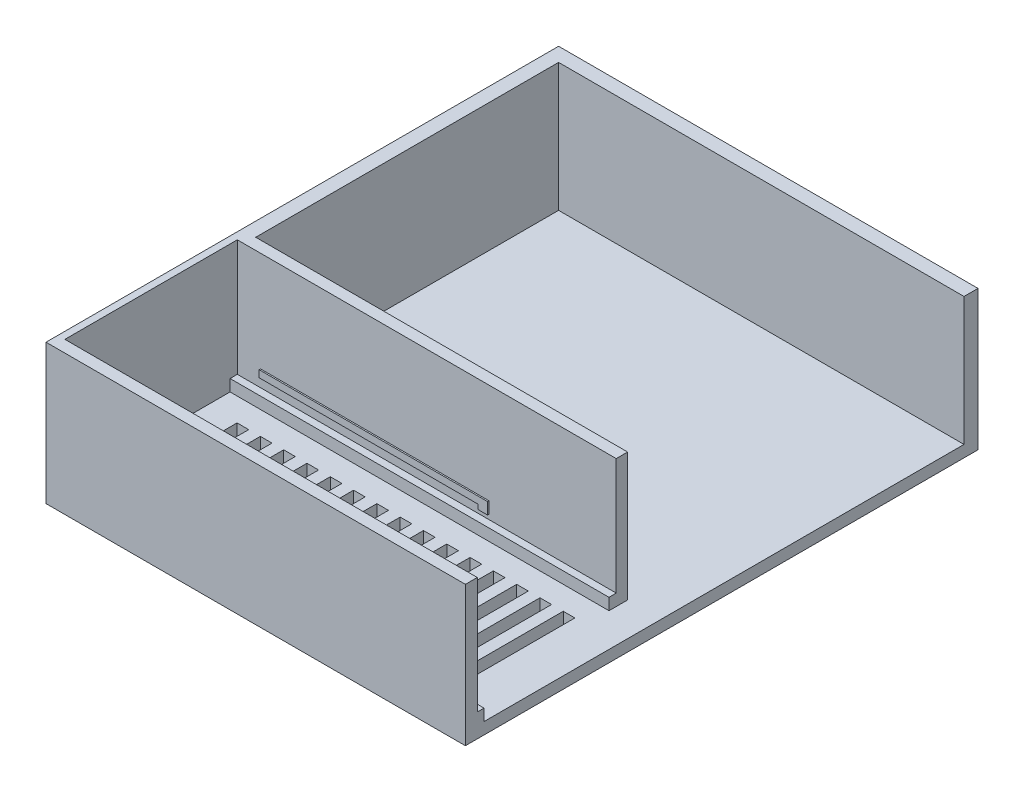
SolidWorks part; units mm, degrees
ref_plane "Front Plane" through (0, 0, 0) normal (0, 0, 1) x (1, 0, 0)
ref_plane "Top Plane" through (0, 0, 0) normal (0, 1, 0) x (1, 0, 0)
ref_plane "Right Plane" through (0, 0, 0) normal (1, 0, 0) x (0, 0, -1)
sketch "Sketch1" plane through (0, 0, 0) normal (0, 1, 0) x (1, 0, 0)
  line L0 (-32, -22) -> (-32, -47)
  line L1 (45, 55) -> (-45, 55)
  line L2 (45, 55) -> (45, -55)
  line L3 (45, -55) -> (-45, -55)
  line L4 (-45, 55) -> (-45, -55)
  line L5 (45, 55) -> (-45, -55) construction
  line L6 (45, -55) -> (-45, 55) construction
  line L7 (-37, -22) -> (-34.5, -22)
  line L8 (-37, -22) -> (-37, -47)
  line L9 (-37, -47) -> (-34.5, -47)
  line L10 (-34.5, -22) -> (-34.5, -47)
  line L11 (-32, -22) -> (-29.5, -22)
  line L12 (-29.5, -22) -> (-29.5, -47)
  line L13 (-32, -47) -> (-29.5, -47)
  line L14 (-27, -22) -> (-27, -47)
  line L15 (-27, -22) -> (-24.5, -22)
  line L16 (-24.5, -22) -> (-24.5, -47)
  line L17 (-27, -47) -> (-24.5, -47)
  line L18 (-22, -22) -> (-22, -47)
  line L19 (-22, -22) -> (-19.5, -22)
  line L20 (-19.5, -22) -> (-19.5, -47)
  line L21 (-22, -47) -> (-19.5, -47)
  line L22 (-17, -22) -> (-17, -47)
  line L23 (-17, -22) -> (-14.5, -22)
  line L24 (-14.5, -22) -> (-14.5, -47)
  line L25 (-17, -47) -> (-14.5, -47)
  line L26 (-12, -22) -> (-12, -47)
  line L27 (-12, -22) -> (-9.5, -22)
  line L28 (-9.5, -22) -> (-9.5, -47)
  line L29 (-12, -47) -> (-9.5, -47)
  line L30 (-7, -22) -> (-7, -47)
  line L31 (-7, -22) -> (-4.5, -22)
  line L32 (-4.5, -22) -> (-4.5, -47)
  line L33 (-7, -47) -> (-4.5, -47)
  line L34 (-2, -22) -> (-2, -47)
  line L35 (-2, -22) -> (0.5, -22)
  line L36 (0.5, -22) -> (0.5, -47)
  line L37 (-2, -47) -> (0.5, -47)
  line L38 (3, -22) -> (3, -47)
  line L39 (3, -22) -> (5.5, -22)
  line L40 (5.5, -22) -> (5.5, -47)
  line L41 (3, -47) -> (5.5, -47)
  line L42 (8, -22) -> (8, -47)
  line L43 (8, -22) -> (10.5, -22)
  line L44 (10.5, -22) -> (10.5, -47)
  line L45 (8, -47) -> (10.5, -47)
  line L46 (13, -22) -> (13, -47)
  line L47 (13, -22) -> (15.5, -22)
  line L48 (15.5, -22) -> (15.5, -47)
  line L49 (13, -47) -> (15.5, -47)
  line L50 (18, -22) -> (18, -47)
  line L51 (18, -22) -> (20.5, -22)
  line L52 (20.5, -22) -> (20.5, -47)
  line L53 (18, -47) -> (20.5, -47)
  line L54 (23, -22) -> (23, -47)
  line L55 (23, -22) -> (25.5, -22)
  line L56 (25.5, -22) -> (25.5, -47)
  line L57 (23, -47) -> (25.5, -47)
  line L58 (28, -22) -> (28, -47)
  line L59 (28, -22) -> (30.5, -22)
  line L60 (30.5, -22) -> (30.5, -47)
  line L61 (28, -47) -> (30.5, -47)
  line L62 (33, -22) -> (33, -47)
  line L63 (33, -22) -> (35.5, -22)
  line L64 (35.5, -22) -> (35.5, -47)
  line L65 (33, -47) -> (35.5, -47)
  point P0 (0, 0)
  point P10 (-35.75, -47)
  dimension "D1" = 110
  dimension "D2" = 90
  dimension "D3" = 8
  dimension "D4" = 8
  dimension "D5" = 25
  dimension "D6" = 2.5
  dimension "D7" = 15
extrude "Boss-Extrude1" add sketch "Sketch1" along normal blind 2.5
sketch "Sketch2" plane through (0, 2.5, 0) normal (0, 1, 0) x (1, 0, 0)
  line L0 (45, -51.673) -> (45, -51)
  line L1 (45, -51) -> (-43.5, -51)
  line L2 (-43.5, -51) -> (-43.5, -17)
  line L3 (-43.5, -17) -> (37.8136, -17)
  line L4 (-45, 55) -> (-45, -55)
  line L5 (-45, -55) -> (45, -55)
  line L6 (45, -55) -> (45, 55)
  line L7 (45, 55) -> (-45, 55)
  line L8 (-45, 55) -> (-45, -55)
  line L9 (-45, -55) -> (45, -55)
  line L10 (45, -55) -> (45, 55)
  line L11 (45, 55) -> (-45, 55)
  line L12 (37.8136, -17) -> (37.8136, -13)
  line L13 (37.8136, -13) -> (-42, -13)
  line L14 (-42, -13) -> (-42, 52)
  line L15 (-42, 52) -> (45, 52)
  point P6 (0, 0)
  dimension "D2" = 4
  dimension "D3" = 1.5
  dimension "D4" = 34
  dimension "D5" = 4
  dimension "D6" = 3
  dimension "D7" = 3
  dimension "D1" = 0
extrude "Boss-Extrude2" add sketch "Sketch2" along normal blind 2.5 contours L14 L15 L10 L11 L8 L9 L0 L1 L2 L3 L12 L13 region at (43.5787, 2.5, 53.3365)
sketch "Sketch4" plane through (0, 5, 0) normal (0, 1, 0) x (1, 0, 0)
  line L0 (-43.5, -51) -> (-43.5, -52.4476)
  line L1 (-43.5, -52.4476) -> (45, -52.4476)
  line L2 (45, -55) -> (45, 55) construction
  line L3 (-43.5, -17) -> (-43.5, -15.4447)
  line L4 (-43.5, -15.4447) -> (37.8136, -15.4447)
  line L5 (37.8136, -17) -> (37.8136, -13) construction
  line L18 (-42, -13) -> (-42, 52)
  line L19 (-42, 52) -> (45, 52)
  line L20 (45, 52) -> (45, 55)
  line L21 (45, 55) -> (-45, 55)
  line L22 (-45, 55) -> (-45, -55)
  line L23 (-45, -55) -> (45, -55)
  line L24 (45, -55) -> (45, -51)
  line L25 (45, -51) -> (-43.5, -51)
  line L26 (-43.5, -51) -> (-43.5, -17)
  line L27 (-43.5, -17) -> (37.8136, -17)
  line L28 (37.8136, -17) -> (37.8136, -13)
  line L29 (37.8136, -13) -> (-42, -13)
  line L30 (-42, -13) -> (-42, 52)
  line L31 (-42, 52) -> (45, 52)
  line L32 (45, 52) -> (45, 55)
  line L33 (45, 55) -> (-45, 55)
  line L34 (-45, 55) -> (-45, -55)
  line L35 (-45, -55) -> (45, -55)
  line L36 (45, -55) -> (45, -52.4476)
  line L38 (-43.5, -51) -> (-43.5, -17)
  line L40 (37.8136, -15.4447) -> (37.8136, -13)
  line L41 (37.8136, -13) -> (-42, -13)
  dimension "D1" = 0
extrude "Boss-Extrude3" add sketch "Sketch4" along normal blind 25
sketch "Sketch5" plane through (0, 0, 52.4476) normal (0, 0, -1) x (-1, 0, 0)
  line L0 (43.5, 30) -> (43.5, 5) construction
  line L1 (38.5, 8.5) -> (-10.5, 8.5)
  line L2 (38.5, 8.5) -> (38.5, 7)
  line L3 (38.5, 7) -> (-8.5, 7)
  line L4 (-10.5, 8.5) -> (-10.5, 7)
  line L5 (-45, 5) -> (43.5, 5) construction
  line L8 (-10.5, 7) -> (-10.5, 6)
  line L9 (-10.5, 6) -> (-8.5, 6)
  line L10 (-8.5, 7) -> (-8.5, 6)
  dimension "D1" = 5
  dimension "D2" = 2
  dimension "D3" = 1.5
  dimension "D4" = 49
  dimension "D5" = 1
  dimension "D6" = 2
extrude "Boss-Extrude4" add sketch "Sketch5" along normal blind 0.3
sketch "Sketch7" plane through (0, 0, 15.4447) normal (0, 0, 1) x (1, 0, 0)
  line L0 (10.5, 8.5) -> (10.5, 6)
  line L1 (10.5, 6) -> (8.5, 6)
  line L2 (8.5, 6) -> (8.5, 7)
  line L3 (8.5, 7) -> (-38.5, 7)
  line L4 (-38.5, 7) -> (-38.5, 8.5)
  line L5 (-38.5, 8.5) -> (10.5, 8.5)
extrude "Boss-Extrude5" add sketch "Sketch7" along normal blind 0.3
sketch "Sketch8" plane through (-42, 0, 0) normal (1, 0, 0) x (0, 0, -1)
  line L0 (19.5, 30) -> (19.5, 2.5) construction
  line L1 (-13, 30) -> (52, 30) construction
  line L2 (-13, 2.5) -> (52, 2.5) construction
  line L4 (-13, 16.25) -> (52, 16.25) construction
  line L5 (-13, 30) -> (-13, 2.5) construction
  line L6 (52, 30) -> (52, 2.5) construction
  line L8 (1, 17.75) -> (2, 17.75)
  line L9 (1, 17.75) -> (1, 14.75)
  line L10 (1, 14.75) -> (2, 14.75)
  line L11 (2, 17.75) -> (2, 14.75)
  line L12 (1, 17.75) -> (2, 14.75) construction
  line L13 (1, 14.75) -> (2, 17.75) construction
  circle A0 centre (-5, 16.25) radius 3
  point P14 (1.5, 16.25)
  point P19 (0, 0)
  dimension "D2" = 6
  dimension "D1" = 8
  dimension "D3" = 1
  dimension "D4" = 3
  dimension "D5" = 6
  dimension "D6" = 6
